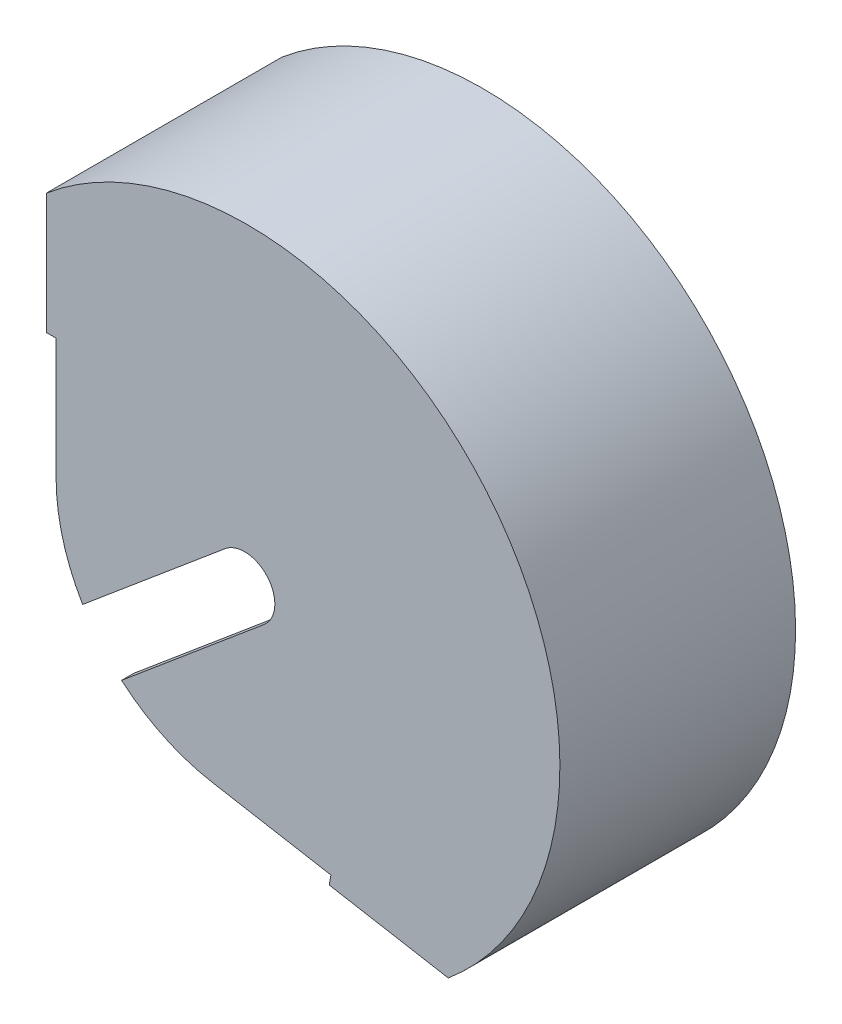
SolidWorks part; units mm, degrees
ref_plane "Front Plane" through (0, 0, 0) normal (0, 0, 1) x (1, 0, 0)
ref_plane "Top Plane" through (0, 0, 0) normal (0, 1, 0) x (1, 0, 0)
ref_plane "Right Plane" through (0, 0, 0) normal (1, 0, 0) x (0, 0, -1)
sketch "Sketch1" plane through (0, 0, 0) normal (0, 0, 1) x (1, 0, 0)
  line L0 (0, 0) -> (-39.624, 0)
  line L1 (0, 0) -> (-6.8806, -39.022)
  line L2 (-39.624, 0) -> (-39.624, 25.4)
  line L3 (-6.8806, -39.022) -> (18.1335, -43.4327)
  line L4 (-39.624, 25.4) -> (-41.656, 25.4)
  line L5 (18.1335, -43.4327) -> (17.7806, -45.4338)
  line L6 (-41.656, 25.4) -> (-41.656, 50.8)
  line L7 (17.7806, -45.4338) -> (42.7947, -49.8445)
  arc A0 (-39.624, 0) -> (-6.8806, -39.022) centre (0, 0) ccw
  arc A1 (42.7947, -49.8445) -> (-41.656, 50.8) centre (0.5694, 0.4778) ccw
  dimension "D1" = 79.248
  dimension "D2" = 80
  dimension "D3" = 25.4
  dimension "D4" = 25.4
  dimension "D5" = 2.032
  dimension "D6" = 2.032
  dimension "D7" = 25.4
extrude "Side" add sketch "Sketch1" along normal blind 2.54 contours L7 A1 L6 L4 L2 L0 L1 L3 L5 | L0 A0 L1 region at (-18.6316, -15.6338, 0) region at (15.1155, 12.6834, 0)
sketch "Sketch2" plane through (0, 0, 2.54) normal (0, 0, 1) x (1, 0, 0)
  line L0 (-40.0233, 48.8542) -> (-41.656, 48.8542)
  line L2 (41.1621, -47.8987) -> (40.8786, -49.5066)
  line L4 (-41.656, 25.4) -> (-41.656, 50.8) construction
  line L5 (17.7806, -45.4338) -> (42.7947, -49.8445) construction
  line L6 (-41.656, 48.8542) -> (-41.656, 50.8)
  line L7 (40.8786, -49.5066) -> (42.7947, -49.8445)
  arc A2 (41.1621, -47.8987) -> (-40.0233, 48.8542) centre (0.5694, 0.4778) ccw
  arc A3 (41.1621, -47.8987) -> (-40.0233, 48.8542) centre (0.5694, 0.4778) ccw
  arc A5 (42.7947, -49.8445) -> (-41.656, 50.8) centre (0.5694, 0.4778) ccw
  arc A6 (42.7947, -49.8445) -> (-41.656, 50.8) centre (0.5694, 0.4778) ccw
  line M6 (18.1335, -43.4327) -> (17.7806, -45.4338)
  line M7 (17.7806, -45.4338) -> (42.7947, -49.8445)
  arc M8 (42.7947, -49.8445) -> (-41.656, 50.8) centre (0.5694, 0.4778) ccw
  line M9 (-41.656, 50.8) -> (-41.656, 25.4)
  line M10 (-41.656, 25.4) -> (-39.624, 25.4)
  dimension "D1" = 2.54
  dimension "D2" = 0
extrude "Cover" add sketch "Sketch2" along normal blind 44.45 contours A3 L2 L0 M6 M7 M8 M9 M10 region at (-40.8397, 50.4387, 2.54)
ref_plane "midplane" through (0, 0, 24.765) normal (0, 0, 1) x (1, 0, 0)
mirror "Mirror1" about plane through (0, 0, 24.765) normal (0, 0, 1) of "Side"
sketch "Sketch3" plane through (0, 0, 49.53) normal (0, 0, 1) x (1, 0, 0)
  line L0 (0, 0) -> (-30.3537, -25.4698) construction
  line L1 (-4.0817, 4.8644) -> (-37.1595, -22.8912)
  line L2 (-37.1595, -22.8912) -> (-28.9961, -32.62)
  line L3 (-28.9961, -32.62) -> (4.0817, -4.8644)
  arc A0 (4.0817, -4.8644) -> (-4.0817, 4.8644) centre (0, 0) ccw
  arc A1 (-39.624, 0) -> (-6.8806, -39.022) centre (0, 0) ccw construction
  dimension "D2" = 12.7
  dimension "D1" = 43.18
extrude "Flywheel slit" cut sketch "Sketch3" against normal up to next
sketch "Sketch4" plane through (0, 0, 0) normal (0, 0, -1) x (-1, 0, 0)
  line L0 (0, 0) -> (39.624, 0) construction
  line L1 (0, 0) -> (33.2775, 10.174) construction
  line L2 (-2.1162, -33.5317) -> (33.2775, 10.174) construction
  line L3 (33.2775, 10.174) -> (3.2382, -36.9452) construction
  line L4 (3.2382, -36.9452) -> (-2.1162, -33.5317) construction
  circle A2 centre (-2.1162, -33.5317) radius 3.2639
  circle A3 centre (33.2775, 10.174) radius 3.2639
  dimension "D1" = 6.35
  dimension "D2" = 55.88
  dimension "D4" = 6.5278
  dimension "D5" = 17
extrude "Mount holes" cut sketch "Sketch4" against normal up to next
